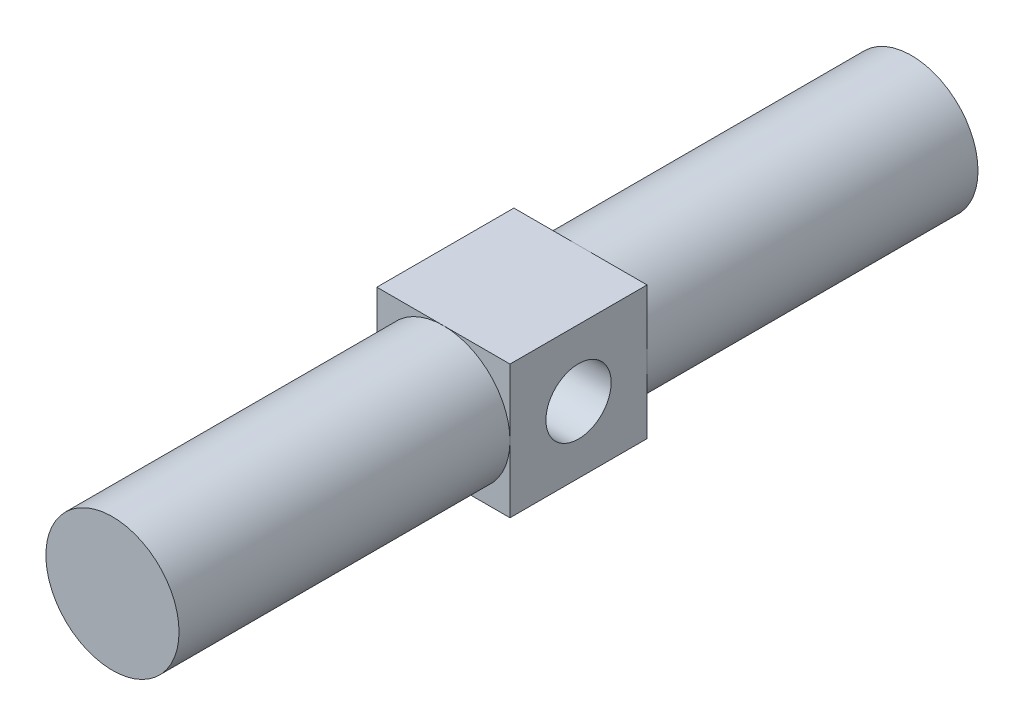
SolidWorks part; units mm, degrees
material "Delrin 2700 NC010, Low Viscosity Acetal Copolymer (SS)"
ref_plane "Front Plane" through (0, 0, 0) normal (0, 0, 1) x (1, 0, 0)
ref_plane "Top Plane" through (0, 0, 0) normal (0, 1, 0) x (1, 0, 0)
ref_plane "Right Plane" through (0, 0, 0) normal (1, 0, 0) x (0, 0, -1)
sketch "Sketch1" plane through (0, 0, 0) normal (0, 0, 1) x (1, 0, 0)
  circle A0 centre (0, 0) radius 6.35
extrude "Boss-Extrude1" add sketch "Sketch1" along normal blind 76.2
sketch "Sketch2" plane through (0, 0, 0) normal (1, 0, 0) x (0, 0, -1)
  line L0 (0, 6.35) -> (-76.2, 6.35) construction
  line L1 (-44.6356, 6.35) -> (-31.5644, 6.35)
  line L2 (-44.6356, 6.35) -> (-44.6356, -6.35)
  line L3 (-44.6356, -6.35) -> (-31.5644, -6.35)
  line L4 (-31.5644, 6.35) -> (-31.5644, -6.35)
  line L5 (-44.6356, 6.35) -> (-31.5644, -6.35) construction
  line L6 (-44.6356, -6.35) -> (-31.5644, 6.35) construction
  line L7 (-76.2, -6.35) -> (0, -6.35) construction
  point P4 (-38.1, 0)
extrude "Boss-Extrude2" add sketch "Sketch2" along normal blind 6.35 and the other way blind 6.35
sketch "Sketch3" plane through (0, 0, 0) normal (1, 0, 0) x (0, 0, -1)
  circle A0 centre (-38.1, 0) radius 3.1115
extrude "Cut-Extrude1" cut sketch "Sketch3" against normal blind 6.35 and the other way blind 6.35
equation "\"3n\"=0.1"
